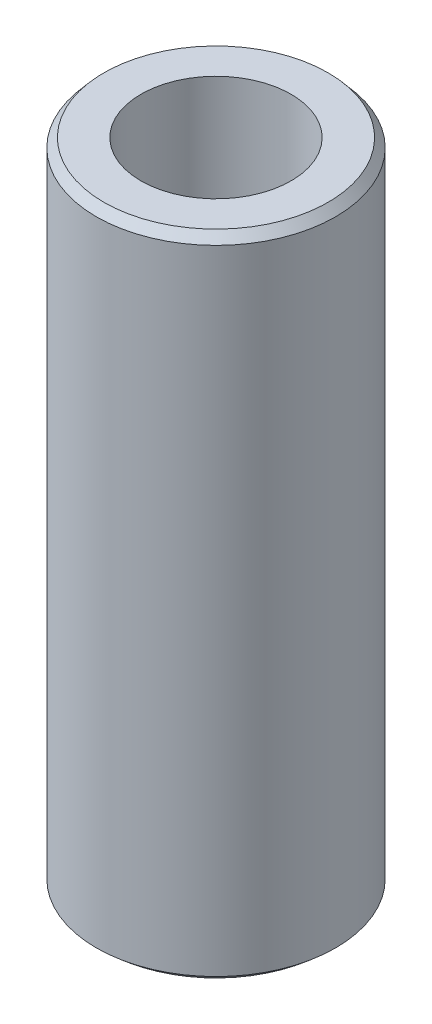
SolidWorks part; units mm, degrees
ref_plane "Front Plane" through (0, 0, 0) normal (0, 0, 1) x (1, 0, 0)
ref_plane "Top Plane" through (0, 0, 0) normal (0, 1, 0) x (1, 0, 0)
ref_plane "Right Plane" through (0, 0, 0) normal (1, 0, 0) x (0, 0, -1)
sketch "Sketch1" plane through (0, 0, 0) normal (0, 1, 0) x (1, 0, 0)
  circle A0 centre (0, 0) radius 37.5
  dimension "SHAFT_OD" = 75
extrude "Boss-Extrude1" add sketch "Sketch1" along normal blind 203.5721
sketch "Sketch2" plane through (0, 0, 0) normal (0, 1, 0) x (1, 0, 0)
  circle A0 centre (0, 0) radius 23.5361
  dimension "BORE_D" = 47.0721
extrude "Cut-Extrude1" cut sketch "Sketch2" along normal through all
chamfer "Chamfer1" distance 2.762 angle 40.359 2 edges at (0, 203.5721, 37.5) (0, 0, 37.5) first distance on face at (0, 203.5721, 37.5) first distance on face at (0, 0, 23.5361)
